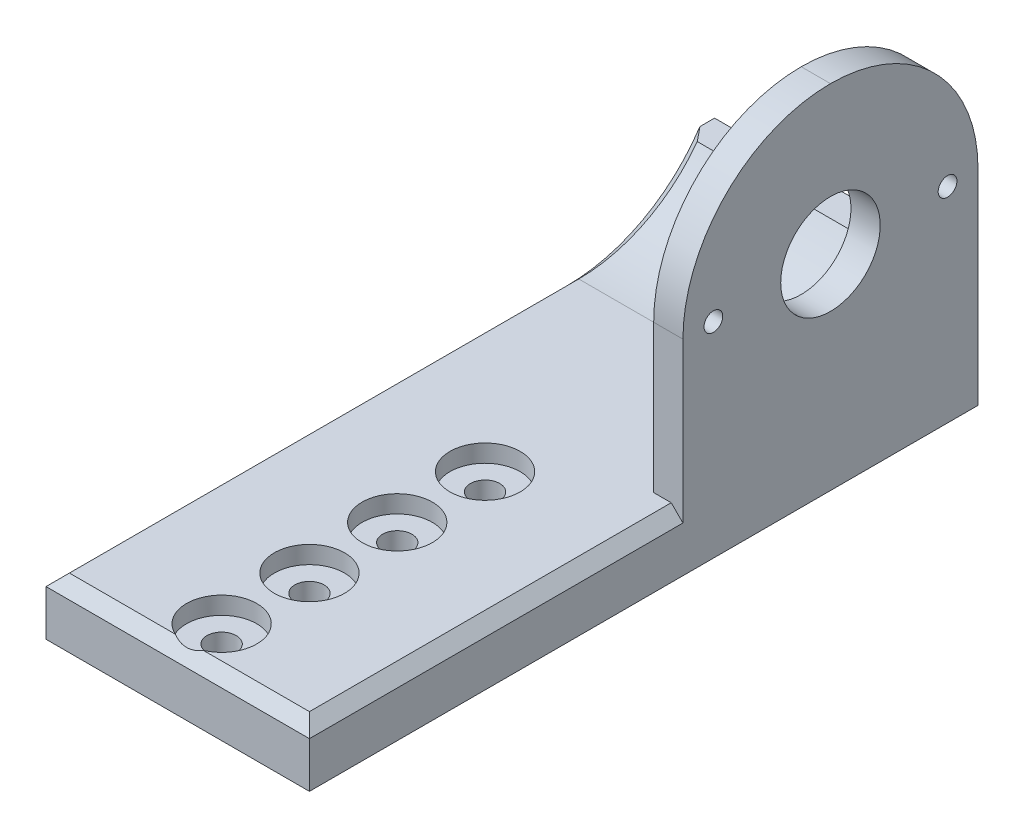
SolidWorks part; units mm, degrees
ref_plane "Front Plane" through (0, 0, 0) normal (0, 0, 1) x (1, 0, 0)
ref_plane "Top Plane" through (0, 0, 0) normal (0, 1, 0) x (1, 0, 0)
ref_plane "Right Plane" through (0, 0, 0) normal (1, 0, 0) x (0, 0, -1)
sketch "Sketch1" plane through (0, 0, 0) normal (0, 1, 0) x (1, 0, 0)
  line L1 (0, 0) -> (57.15, 0)
  line L2 (0, 0) -> (0, 145.034)
  line L3 (0, 145.034) -> (57.15, 145.034)
  line L4 (57.15, 0) -> (57.15, 145.034)
  dimension "D1" = 57.15
  dimension "D2" = 145.034
extrude "Boss-Extrude1" add sketch "Sketch1" along normal blind 25.4
sketch "Sketch3" plane through (57.15, 0, 0) normal (1, 0, 0) x (0, 0, -1)
  line L0 (0, 0) -> (145.034, 0) construction
  line L1 (145.034, 25.4) -> (145.034, 0) construction
  circle A0 centre (113.03, 44.45) radius 32.004
  dimension "D1" = 64.008
  dimension "D2" = 44.45
  dimension "D3" = 32.004
extrude "Cut-Extrude2" cut sketch "Sketch3" against normal through all
sketch "Sketch4" plane through (0, 0, 0) normal (0, -1, 0) x (-1, 0, 0)
  line L0 (0, 0) -> (-57.15, 0) construction
  line L1 (-57.15, 0) -> (-57.15, 145.034) construction
  circle A0 centre (-28.575, 9.525) radius 3.175
  circle A1 centre (-28.575, 28.575) radius 3.175
  circle A2 centre (-28.575, 47.625) radius 3.175
  circle A3 centre (-28.575, 66.675) radius 3.175
  dimension "D1" = 6.35
  dimension "D2" = 6.35
  dimension "D3" = 6.35
  dimension "D4" = 6.35
  dimension "D5" = 19.05
  dimension "D6" = 19.05
  dimension "D7" = 19.05
  dimension "D8" = 9.525
  dimension "D9" = 28.575
  dimension "D10" = 28.575
  dimension "D11" = 28.575
  dimension "D12" = 28.575
extrude "Cut-Extrude3" cut sketch "Sketch4" against normal through all
sketch "Sketch7" plane through (0, 0, 0) normal (0, -1, 0) x (1, 0, 0)
  line L0 (57.15, 0) -> (57.15, -145.034) construction
  line L1 (57.15, -81.026) -> (50.8, -81.026)
  line L2 (57.15, -81.026) -> (57.15, -145.034)
  line L3 (57.15, -145.034) -> (50.8, -145.034)
  line L4 (50.8, -81.026) -> (50.8, -145.034)
  line L8 (57.15, -145.034) -> (0, -145.034) construction
  dimension "D1" = 6.35
  dimension "D2" = 64.008
  dimension "D3" = 0
extrude "Boss-Extrude2" add sketch "Sketch7" against normal blind 76.454
fillet "Fillet1" radius 32.004 2 edges at (53.975, 76.454, -145.034) (53.975, 76.454, -81.026)
sketch "Sketch9" plane through (50.8, 0, 0) normal (-1, 0, 0) x (0, 0, 1)
  circle A1 centre (-113.03, 44.45) radius 10.795
  circle A2 centre (-138.43, 44.45) radius 2.032
  circle A3 centre (-87.63, 44.45) radius 2.032
  dimension "D1" = 21.59
  dimension "D4" = 4.064
  dimension "D5" = 4.064
  dimension "D2" = 25.4
  dimension "D3" = 25.4
  dimension "D6" = 32.004
  dimension "D7" = 32.004
  dimension "D8" = 32.004
  dimension "D9" = 32.004
extrude "Cut-Extrude5" cut sketch "Sketch9" against normal blind 76.454
sketch "Sketch10" plane through (0, 25.4, 0) normal (0, 1, 0) x (1, 0, 0)
  line L1 (50.8, 113.03) -> (0, 113.03)
  line L2 (50.8, 113.03) -> (50.8, 81.026)
  line L3 (50.8, 0) -> (0, 0)
  line L4 (0, 113.03) -> (0, 0)
  line L5 (57.15, 81.026) -> (50.8, 81.026)
  line L6 (57.15, 81.026) -> (57.15, 0)
  line L7 (57.15, 0) -> (50.8, 0)
extrude "Cut-Extrude7" cut sketch "Sketch10" against normal blind 12.954
sketch "Sketch11" plane through (0, 12.446, 0) normal (0, 1, 0) x (1, 0, 0)
  circle A0 centre (28.575, 66.675) radius 7.62
  circle A1 centre (28.575, 47.625) radius 7.62
  circle A2 centre (28.575, 28.575) radius 7.62
  circle A3 centre (28.575, 9.525) radius 7.62
  dimension "D1" = 15.24
  dimension "D2" = 15.24
  dimension "D3" = 15.24
  dimension "D4" = 15.24
extrude "Cut-Extrude8" cut sketch "Sketch11" against normal blind 3.81
chamfer "Chamfer1" distance 2.54 angle 45 4 edges at (0, 15.8674, -127.4276) (0, 12.446, -56.515) (28.575, 12.446, 0) (57.15, 12.446, -40.513)
